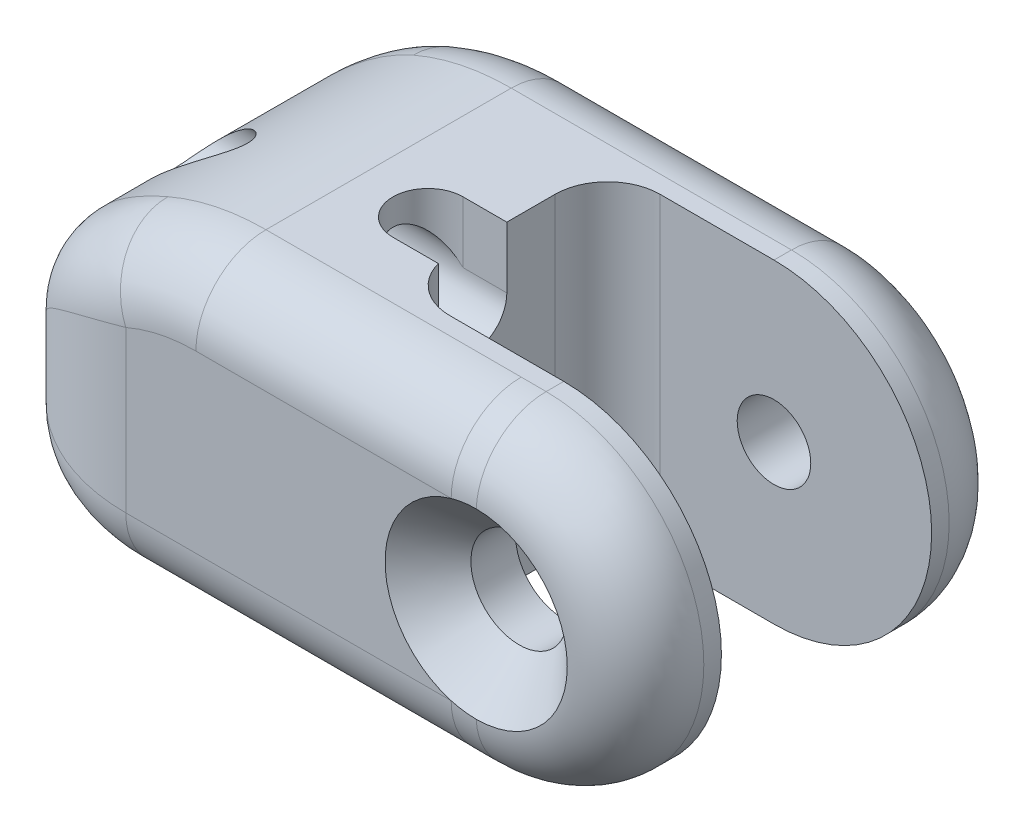
SolidWorks part; units mm, degrees
ref_plane "Front Plane" through (0, 0, 0) normal (0, 0, 1) x (1, 0, 0)
ref_plane "Top Plane" through (0, 0, 0) normal (0, 1, 0) x (1, 0, 0)
ref_plane "Right Plane" through (0, 0, 0) normal (1, 0, 0) x (0, 0, -1)
sketch "Sketch2" plane through (0, 0, 0) normal (0, 1, 0) x (1, 0, 0)
  line L0 (-5.5, 11) -> (23.5, 11)
  line L1 (23.5, 11) -> (23.5, 6)
  line L2 (23.5, 6) -> (8, 6)
  line L3 (5, 3) -> (5, -3)
  line L4 (8, -6) -> (23.5, -6)
  line L5 (23.5, -6) -> (23.5, -11)
  line L8 (-49.3622, 0) -> (56.3776, 0) construction
  line L9 (0, 21.2372) -> (0, -19.0689) construction
  line L10 (5, 3) -> (8, 3) construction
  line L11 (8, 3) -> (8, 6) construction
  line L16 (-5.5, -11) -> (23.5, -11)
  arc A0 (8, 6) -> (5, 3) centre (8, 3) ccw
  arc A1 (8, -6) -> (5, -3) centre (8, -3) cw
  arc A3 (-5.5, 11) -> (-5.5, -11) centre (-5.5, 0) ccw
  point P13 (8, 3)
  dimension "D2" = 22
  dimension "D3" = 5
  dimension "D4" = 18.5
  dimension "D5" = 12
  dimension "D6" = 3
  dimension "D7" = 3
  dimension "D8" = 5
  dimension "D9" = 29
extrude "Boss-Extrude1" add sketch "Sketch2" along normal blind 18
sketch "Sketch5" plane through (0, 0, 11) normal (0, 0, 1) x (1, 0, 0)
  line L0 (-13.5058, 9) -> (31.8434, 9) construction
  line L1 (-5.5, 18) -> (-5.5, 0) construction
  line L2 (23.5, 18) -> (23.5, 0) construction
  line L3 (-5.5, 18) -> (23.5, 18) construction
  line L4 (14.5, 18) -> (14.5, 0) construction
  line L5 (-16.5, 0) -> (-5.5, 0) construction
  line L7 (-15.5, 0) -> (-15.5, 4)
  line L8 (-15.5, 0) -> (14.5, 0)
  line L9 (-1.5, 18) -> (14.5, 18)
  arc A1 (14.5, 0) -> (14.5, 18) centre (14.5, 9) ccw
  arc A2 (-1.5, 18) -> (-15.5, 4) centre (-1.5, 4) ccw
  dimension "D2" = 4
  dimension "D1" = 9
  dimension "D3" = 10
extrude "Cut-Extrude1" cut sketch "Sketch5" against normal blind 22 flip side to cut
sketch "Sketch6" plane through (0, 0, 11) normal (0, 0, 1) x (1, 0, 0)
  line L0 (14.5, 0) -> (14.5, 18) construction
  point P4 (14.5, 9)
hole_wizard "CSK for M5 Countersunk Flat Head Screw1" positions "Sketch7" profile "Sketch8" countersink size "M5" standard "DIN" end condition up to next
sketch "Sketch7" plane through (0, 0, 11) normal (0, 0, 1) x (1, 0, 0)
  point P0 (14.5, 9)
sketch "Sketch8" plane through (14.5, 9, 11) normal (1, 0, 0) x (0, -1, 0)
  line L0 (0, 0) -> (0, 5)
  line L1 (0, 5) -> (2.75, 5)
  line L2 (2.75, 5) -> (2.75, 2.45)
  line L3 (2.75, 2.45) -> (5.2, 0)
  line L5 (5.2, 0) -> (0, 0)
  line L6 (-2.75, 2.45) -> (-5.2, 0) construction
  line L11 (0, -6.35) -> (0, 107.95) construction
  dimension "Thru Hole Dia." = 5.5
  dimension "Thru Hole Depth" = 5
  dimension "Near C'Sink Dia." = 10.4
  dimension "Near C'Sink Angle" = 90
hole_wizard "M5 Tapped Hole1" positions "Sketch9" profile "Sketch11" tap size "M5" standard "DIN" end condition through all
sketch "Sketch9" plane through (0, 0, 11) normal (0, 0, 1) x (1, 0, 0)
  point P0 (14.5, 9)
sketch "Sketch11" plane through (14.5, 9, 11) normal (1, 0, 0) x (0, -1, 0)
  line L0 (0, 0) -> (0, 22)
  line L1 (0, 22) -> (2.1, 22)
  line L2 (2.1, 22) -> (2.1, 3.1)
  line L3 (2.1, 3.1) -> (5.2, 0)
  line L5 (5.2, 0) -> (0, 0)
  line L6 (-2.1, 3.1) -> (-5.2, 0) construction
  line L11 (0, -6.35) -> (0, 107.95) construction
  dimension "Thru Tap Drill Dia." = 4.2
  dimension "Thru Tap Drill Depth" = 22
  dimension "Near C'Sink Dia." = 10.4
  dimension "Near C'Sink Angle" = 90
cosmetic thread "Hole Thread1" parameters "D2"=5
sketch "Sketch13" plane through (5, 0, 0) normal (1, 0, 0) x (0, 0, -1)
  line L0 (-1.75, -2.2721) -> (-1.75, 20.0856) construction
  line L1 (-3, 0) -> (3, 0) construction
  line L2 (-3, 18) -> (3, 18) construction
  circle A0 centre (-1.75, 14.5) radius 2
  point P4 (0, 0)
  dimension "D2" = 3.5
  dimension "D3" = 4
  dimension "D1" = 1.75
extrude "Cut-Extrude2" cut sketch "Sketch13" against normal through all both and the other way through all
sketch "Sketch14" plane through (0, 18, 0) normal (0, 1, 0) x (1, 0, 0)
  line L0 (5, 0) -> (-14.1432, 0) construction
  line L3 (5, -3) -> (5, 3) construction
  line L4 (2.5, -3.75) -> (7.4532, -3.75)
  line L5 (2.5, 0.25) -> (7.4532, 0.25)
  line L6 (7.4532, 0.25) -> (7.4532, -3.75)
  arc A0 (2.5, 0.25) -> (2.5, -3.75) centre (2.5, -1.75) ccw
  dimension "D1" = 1.75
  dimension "D2" = 2.5
extrude "Cut-Extrude3" cut sketch "Sketch14" against normal blind 3.5
fillet "Fillet2" radius 4 12 edges at (-11.441, 0, -9.2577) (4.5, 0, -11) (23.5, 9, -11) (6.5, 18, -11) (-3.5212, 17.8533, -11) (-11.441, 0, 9.2577) (4.5, 0, 11) (6.5, 18, 11) (-3.5212, 17.8533, 11) (-15.5, 0, 0) (-14.2361, 9.8131, -6.6844) (-14.2368, 9.8116, 6.6835)
